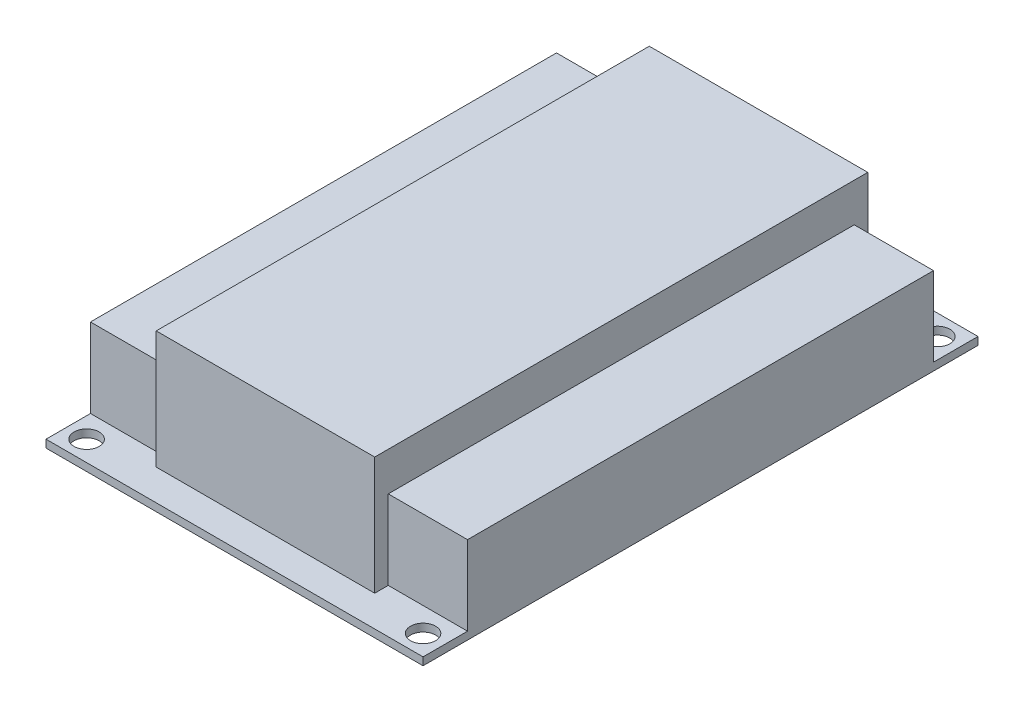
SolidWorks part; units mm, degrees
ref_plane "Front Plane" through (0, 0, 0) normal (0, 0, 1) x (1, 0, 0)
ref_plane "Top Plane" through (0, 0, 0) normal (0, 1, 0) x (1, 0, 0)
ref_plane "Right Plane" through (0, 0, 0) normal (1, 0, 0) x (0, 0, -1)
sketch "Sketch1" plane through (0, 0, 0) normal (0, 1, 0) x (1, 0, 0)
  line L0 (-25.3397, 30.3097) -> (-14.9257, 30.3097)
  line L1 (-25.3397, 36.1517) -> (24.1903, 36.1517)
  line L2 (-25.3397, 36.1517) -> (-25.3397, -36.7463)
  line L3 (-25.3397, -36.7463) -> (24.1903, -36.7463)
  line L4 (24.1903, 36.1517) -> (24.1903, -36.7463)
  line L5 (-14.9257, 32.0877) -> (13.7763, 32.0877)
  line L6 (-14.9257, -32.6823) -> (13.7763, -32.6823)
  line L7 (-25.3397, -30.9043) -> (-14.9257, -30.9043)
  line L8 (-14.9257, 32.0877) -> (-14.9257, -32.6823)
  line L9 (13.7763, 32.0877) -> (13.7763, -32.6823)
  line L10 (13.7763, 30.3097) -> (24.1903, 30.3097)
  line L11 (13.7763, -30.9043) -> (24.1903, -30.9043)
  circle A0 centre (-22.6727, 33.4847) radius 1.651
  circle A1 centre (21.5233, 33.4847) radius 1.651
  circle A2 centre (21.5233, -34.0793) radius 1.651
  circle A3 centre (-22.6727, -34.0793) radius 1.651
  dimension "D9" = 2.667
  dimension "D10" = 2.667
  dimension "D12" = 2.667
  dimension "D1" = 72.898
  dimension "D2" = 49.53
  dimension "D3" = 5.842
  dimension "D4" = 4.064
  dimension "D5" = 4.064
  dimension "D6" = 5.842
  dimension "D7" = 10.414
  dimension "D8" = 10.414
  dimension "D11" = 2.667
extrude "Boss-Extrude1" add sketch "Sketch1" along normal blind 16.51 contours L9 L5 L8 L6 region at (-0.5747, 0, 0.2973)
extrude "Boss-Extrude2" add sketch "Sketch1<6>" along normal blind 11.43 contours L8 L0 L2 L7 | L9 L11 L4 L10 region at (-20.1327, 0, 0.2973) region at (18.9833, 0, 0.2973)
sketch "Sketch1<6>" plane through (0, 0, 0) normal (0, 1, 0) x (1, 0, 0) same geometry as "Sketch1"
extrude "Boss-Extrude3" add sketch "Sketch1<7>" along normal blind 1.016 contours L9 L10 L4 L1 L2 L0 L8 L5 A1 A0 | L11 L9 L6 L8 L7 L2 L3 L4 A3 A2 region at (-0.5747, 0, -33.6798) region at (-0.5747, 0, 34.2745)
sketch "Sketch1<7>" plane through (0, 0, 0) normal (0, 1, 0) x (1, 0, 0) same geometry as "Sketch1"
